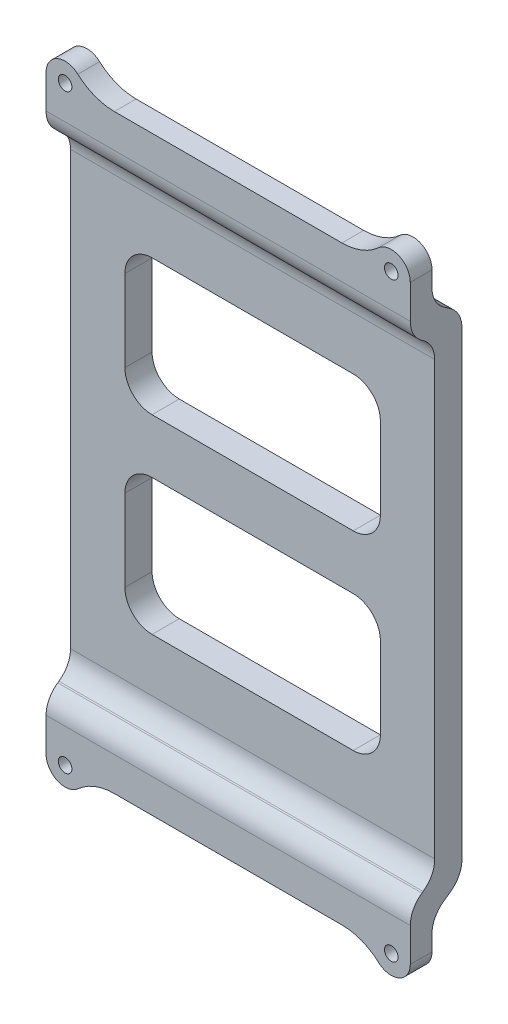
SolidWorks part; units mm, degrees
material "ABS"
ref_plane "Front Plane" through (0, 0, 0) normal (0, 0, 1) x (1, 0, 0)
ref_plane "Top Plane" through (0, 0, 0) normal (0, 1, 0) x (1, 0, 0)
ref_plane "Right Plane" through (0, 0, 0) normal (1, 0, 0) x (0, 0, -1)
sketch "Sketch1" plane through (0, 0, 0) normal (0, 0, 1) x (1, 0, 0)
  line L1 (-30, 54.33) -> (30, 54.33) construction
  line L2 (-30, 54.33) -> (-30, -54.33) construction
  line L3 (-30, -54.33) -> (30, -54.33) construction
  line L4 (30, 54.33) -> (30, -54.33) construction
  circle A0 centre (-30, 54.33) radius 1.25
  circle A1 centre (30, 54.33) radius 1.25
  circle A2 centre (30, -54.33) radius 1.25
  circle A3 centre (-30, -54.33) radius 1.25
  circle A4 centre (-30, 54.33) radius 3.5
  circle A5 centre (30, 54.33) radius 3.5
  circle A6 centre (30, -54.33) radius 3.5
  circle A7 centre (-30, -54.33) radius 3.5
  point P4 (-30, 0)
  point P7 (0, 54.33)
  dimension "D3" = 2.5
  dimension "D4" = 7
  dimension "D1" = 60
  dimension "D2" = 108.66
extrude "MOUNTING BOSSES" add sketch "Sketch1" along normal blind 4
sketch "Sketch4" plane through (0, 0, 0) normal (1, 0, 0) x (0, 0, -1)
  line L0 (-4, 54.33) -> (-4, 45.5226)
  line L1 (-4, 57.83) -> (-4, 50.83) construction
  line L2 (-4, 45.5226) -> (0.5, 42.3889)
  line L3 (0.5, 42.3889) -> (0.5, -42.3889)
  line L4 (0.5, -42.3889) -> (-4, -45.5226)
  line L5 (-4, -45.5226) -> (-4, -54.33)
  line L6 (-4, -50.83) -> (-4, -57.83) construction
  line L7 (-4, -54.33) -> (0, -54.33)
  line L8 (0, -57.83) -> (0, -50.83) construction
  line L9 (0, -54.33) -> (0, -48.83)
  line L10 (0, -48.83) -> (5.5, -45)
  line L11 (5.5, -45) -> (5.5, 45)
  line L12 (5.5, 45) -> (0, 48.83)
  line L13 (0, 48.83) -> (0, 54.33)
  line L14 (0, 54.33) -> (-4, 54.33)
  line L15 (0, 50.83) -> (0, 57.83) construction
  line L16 (0, -50.83) -> (-4, -50.83) construction
  point P21 (7.3933, -46.4276)
  point P22 (5.5, 0)
  point P23 (-2.0593, 49.5955)
  point P24 (0, 52)
  point P25 (0, 48.7752)
  point P27 (0, -48.9259)
  point P31 (0.5, 45)
  point P32 (-4, 48.83)
  dimension "D1" = 90
  dimension "D2" = 2
  dimension "D3" = 2
  dimension "D4" = 5
  dimension "D5" = 9.5
  dimension "D6" = 5
  dimension "D7" = 5
extrude "MATERIAL BULK" add sketch "Sketch4" along normal mid plane 67
sketch "Sketch5" plane through (0, 0, 0) normal (0, 0, 1) x (1, 0, 0)
  line L0 (-28.75, 54.33) -> (-31.25, 54.33) construction
  line L1 (31.25, 54.33) -> (28.75, 54.33) construction
  line L2 (31.25, -54.33) -> (28.75, -54.33) construction
  line L3 (-28.75, -54.33) -> (-31.25, -54.33) construction
  circle A0 centre (-30, 54.33) radius 1.25
  circle A1 centre (30, 54.33) radius 1.25
  circle A2 centre (30, -54.33) radius 1.25
  circle A3 centre (-30, -54.33) radius 1.25
extrude "MOUNT POINT CUT REPEAT" cut sketch "Sketch5" along normal blind 67
sketch "Sketch6" plane through (0, 0, 0) normal (0, 0, 1) x (1, 0, 0)
  line L0 (-33.5, 42.3889) -> (-33.5, -42.3889) construction
  line L1 (-18.5, 30) -> (18.5, 30)
  line L2 (-23.5, 25) -> (-23.5, 10)
  line L3 (-18.5, 5) -> (18.5, 5)
  line L4 (23.5, 25) -> (23.5, 10)
  line L5 (5.225, 0) -> (-5.225, 0) construction
  line L6 (-18.5, -5) -> (18.5, -5)
  line L7 (23.5, -25) -> (23.5, -10)
  line L8 (-18.5, -30) -> (18.5, -30)
  line L9 (-23.5, -25) -> (-23.5, -10)
  arc A0 (18.5, 30) -> (23.5, 25) centre (18.5, 25) cw
  arc A1 (18.5, 5) -> (23.5, 10) centre (18.5, 10) ccw
  arc A2 (-23.5, 10) -> (-18.5, 5) centre (-18.5, 10) ccw
  arc A3 (-18.5, 30) -> (-23.5, 25) centre (-18.5, 25) ccw
  arc A4 (18.5, -5) -> (23.5, -10) centre (18.5, -10) cw
  arc A5 (18.5, -30) -> (23.5, -25) centre (18.5, -25) ccw
  arc A6 (-23.5, -10) -> (-18.5, -5) centre (-18.5, -10) cw
  arc A7 (-18.5, -30) -> (-23.5, -25) centre (-18.5, -25) cw
  point P4 (0, 5)
  dimension "D4" = 5
  dimension "D1" = 30
  dimension "D2" = 5
  dimension "D3" = 10
extrude "WEIGHT RELIEF" cut sketch "Sketch6" against normal blind 67
fillet "Fillet2" radius 5 8 edges at (0, -45, -5.5) (0, -48.83, 0) (0, -45.5226, 4) (0, -42.3889, -0.5) (0, 42.3889, -0.5) (0, 45.5226, 4) (0, 45, -5.5) (0, 48.83, 0)
fillet "Fillet3" radius 10 4 edges at (-26.5, -54.33, 2) (26.5, -54.33, 2) (-26.5, 54.33, 2) (26.5, 54.33, 2)
